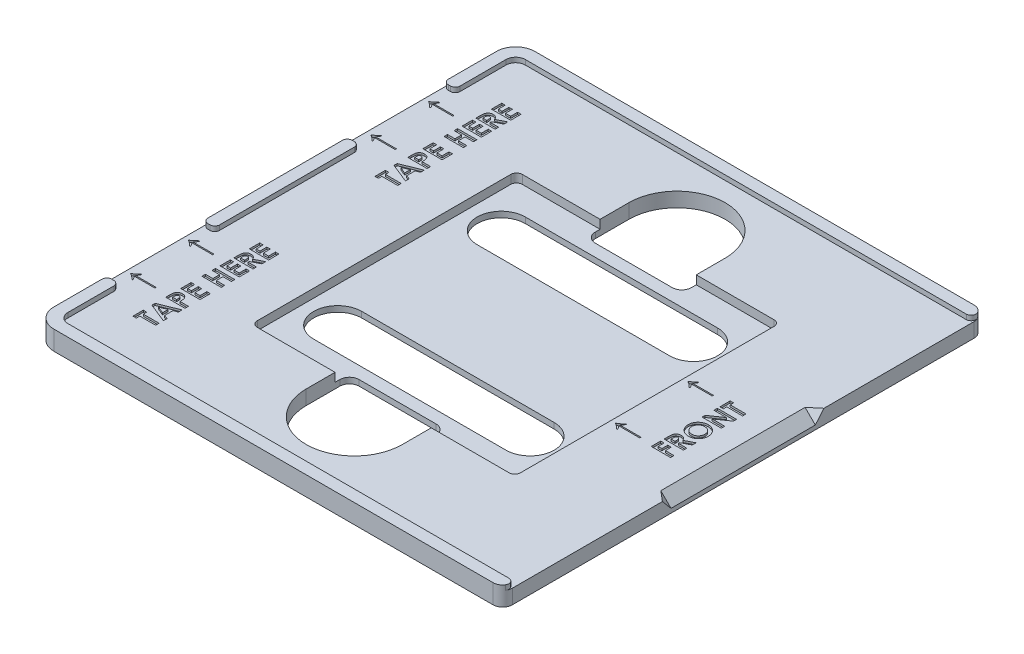
SolidWorks part; units mm, degrees
ref_plane "Front Plane" through (0, 0, 0) normal (0, 0, 1) x (1, 0, 0)
ref_plane "Top Plane" through (0, 0, 0) normal (0, 1, 0) x (1, 0, 0)
ref_plane "Right Plane" through (0, 0, 0) normal (1, 0, 0) x (0, 0, -1)
sketch "Sketch1" plane through (0, 0, 0) normal (0, 1, 0) x (1, 0, 0)
  line L1 (-50, -50) -> (50, -50)
  line L2 (-50, -50) -> (-50, 50)
  line L3 (-50, 50) -> (50, 50)
  line L4 (50, -50) -> (50, 50)
  line L5 (-50, -50) -> (50, 50) construction
  line L6 (-50, 50) -> (50, -50) construction
  point P0 (0, 0)
  dimension "D1" = 100
  dimension "D2" = 100
extrude "Boss-Extrude1" add sketch "Sketch1" along normal blind 3
sketch "Sketch2" plane through (0, 3, 0) normal (0, 1, 0) x (1, 0, 0)
  line L0 (-26.17, 27.35) -> (26.17, 27.35)
  line L1 (-26.17, 27.35) -> (26.17, 27.35) construction
  line L2 (27.17, 26.35) -> (27.17, -26.35)
  line L3 (27.17, 26.35) -> (27.17, -26.35) construction
  line L4 (26.17, -27.35) -> (-26.17, -27.35)
  line L5 (26.17, -27.35) -> (-26.17, -27.35) construction
  line L6 (-27.17, -26.35) -> (-27.17, 26.35)
  line L7 (-27.17, -26.35) -> (-27.17, 26.35) construction
  line L8 (-26.17, 27.55) -> (26.17, 27.55)
  line L9 (27.37, 26.35) -> (27.37, -26.35)
  line L10 (26.17, -27.55) -> (-26.17, -27.55)
  line L11 (-27.37, -26.35) -> (-27.37, 26.35)
  line L12 (-10, -27.55) -> (-10, -33.55)
  line L13 (-10, -33.55) -> (10, -33.55) construction
  line L14 (10, -33.55) -> (10, -27.55)
  line L15 (-27.37, 0) -> (27.37, 0) construction
  line L16 (-10, 33.55) -> (10, 33.55) construction
  line L17 (10, 33.55) -> (10, 27.55)
  line L18 (-10, 27.55) -> (-10, 33.55)
  arc A0 (-26.17, 27.35) -> (-27.17, 26.35) centre (-26.17, 26.35) ccw
  arc A1 (-26.17, 27.35) -> (-27.17, 26.35) centre (-26.17, 26.35) ccw construction
  arc A2 (27.17, 26.35) -> (26.17, 27.35) centre (26.17, 26.35) ccw
  arc A3 (27.17, 26.35) -> (26.17, 27.35) centre (26.17, 26.35) ccw construction
  arc A4 (26.17, -27.35) -> (27.17, -26.35) centre (26.17, -26.35) ccw
  arc A5 (26.17, -27.35) -> (27.17, -26.35) centre (26.17, -26.35) ccw construction
  arc A6 (-27.17, -26.35) -> (-26.17, -27.35) centre (-26.17, -26.35) ccw
  arc A7 (-27.17, -26.35) -> (-26.17, -27.35) centre (-26.17, -26.35) ccw construction
  arc A8 (27.37, 26.35) -> (26.17, 27.55) centre (26.17, 26.35) ccw
  arc A9 (26.17, -27.55) -> (27.37, -26.35) centre (26.17, -26.35) ccw
  arc A10 (-27.37, -26.35) -> (-26.17, -27.55) centre (-26.17, -26.35) ccw
  arc A11 (-26.17, 27.55) -> (-27.37, 26.35) centre (-26.17, 26.35) ccw
  arc A12 (10, -33.55) -> (-10, -33.55) centre (0, -33.55) cw
  arc A13 (10, 33.55) -> (-10, 33.55) centre (0, 33.55) ccw
  point P29 (0, 0)
  point P30 (0, 0)
  point P31 (27.37, 0)
  dimension "D4" = 27.37
  dimension "D2" = 6
  dimension "D3" = 20
  dimension "D1" = 0.2
extrude "Cut-Extrude1" cut sketch "Sketch2" against normal blind 1.8 contours A12 L14 L10 L12 | L17 A13 L18 L8 | L8 A11 L11 A10 L10 A9 L9 A8
sketch "Sketch3" plane through (0, 3, 0) normal (0, 1, 0) x (1, 0, 0)
  line L0 (50, 50) -> (-50, 50) construction
  line L1 (50, -50) -> (47.3, -50)
  line L2 (50, -50) -> (50, 50)
  line L3 (50, 50) -> (47.3, 50)
  line L4 (47.3, -50) -> (47.3, 50)
  line L5 (50, -50) -> (47.3, 50) construction
  line L6 (50, 50) -> (47.3, -50) construction
  point P4 (48.65, 0)
  dimension "D1" = 2.7
extrude "Cut-Extrude3" cut sketch "Sketch3" against normal through all
sketch "Sketch4" plane through (0, 1.2, 0) normal (0, 1, 0) x (1, 0, 0)
  line L0 (-27.17, 0) -> (27.37, 0) construction
  line L3 (0, -27.35) -> (0, 27.35) construction
  line L6 (-27.17, -17) -> (27.37, -17) construction
  line L7 (-27.17, 17) -> (27.37, 17) construction
  line L8 (-20, -17) -> (20, -17) construction
  line L9 (-20, -12) -> (20, -12)
  line L10 (-20, -22) -> (20, -22)
  line L11 (-20, 17) -> (20, 17) construction
  line L12 (-20, 22) -> (20, 22)
  line L13 (-20, 12) -> (20, 12)
  line L14 (26.17, -27.35) -> (-26.17, -27.35) construction
  line L15 (27.37, 26.35) -> (27.37, -26.35) construction
  line L16 (-26.17, 27.35) -> (26.17, 27.35) construction
  line L17 (-27.17, -26.35) -> (-27.17, 26.35) construction
  arc A0 (-20, -12) -> (-20, -22) centre (-20, -17) ccw
  arc A1 (20, -22) -> (20, -12) centre (20, -17) ccw
  arc A2 (-20, 22) -> (-20, 12) centre (-20, 17) ccw
  arc A3 (20, 12) -> (20, 22) centre (20, 17) ccw
  point P2 (0, 0)
  point P3 (-27.17, 17)
  point P4 (0, 0)
  point P5 (27.37, 17)
  point P8 (0, 0)
  point P9 (0, -27.35)
  point P10 (0, 0)
  point P11 (0, 27.4617)
  point P18 (0, -17)
  point P23 (0, 17)
  point P30 (0, 0)
  point P33 (0, 0)
  point P34 (27.37, -17)
  point P37 (0, 0)
  point P38 (0, 0)
  point P39 (0, 0)
  point P40 (27.37, 0)
  point P41 (0, 0)
  point P42 (0, 27.35)
  point P45 (0, 0)
  point P46 (-27.17, -17)
  point P49 (0, 0)
  point P50 (-27.17, 0)
  point P51 (0, 0)
  dimension "D1" = 17
  dimension "D2" = 17
  dimension "D3" = 40
  dimension "D4" = 10
  dimension "D5" = 40
  dimension "D6" = 10
extrude "Cut-Extrude4" cut sketch "Sketch4" against normal through all
sketch "Sketch6" plane through (0, 1.2, 0) normal (0, 1, 0) x (1, 0, 0)
  line L27 (10, -33.55) -> (10, -27.55)
  line L28 (-10, -27.55) -> (-10, -33.55)
  line L29 (10, -33.55) -> (10, -27.55)
  line L30 (-10, -27.55) -> (-10, -33.55)
  line L33 (-10, 27.55) -> (10, 27.55)
  line L34 (10, -27.55) -> (-10, -27.55)
  line L35 (-10, 27.55) -> (-10, 33.55)
  line L36 (10, 33.55) -> (10, 27.55)
  line L37 (-10, 27.55) -> (-10, 33.55)
  line L38 (10, 33.55) -> (10, 27.55)
  arc A13 (-10, -33.55) -> (10, -33.55) centre (0, -33.55) ccw
  arc A14 (-10, -33.55) -> (10, -33.55) centre (0, -33.55) ccw
  arc A17 (10, 33.55) -> (-10, 33.55) centre (0, 33.55) ccw
  arc A18 (10, 33.55) -> (-10, 33.55) centre (0, 33.55) ccw
  point P0 (-9.987, -27.55)
  dimension "D1" = 0
  dimension "D2" = 0
extrude "Cut-Extrude5" cut sketch "Sketch6" against normal through all
sketch "Sketch7" plane through (0, 0, 27.55) normal (0, 0, 1) x (1, 0, 0)
  line L1 (-10, 0) -> (10, 0)
  line L2 (-10, 0) -> (-10, 1.2)
  line L3 (-10, 1.2) -> (10, 1.2)
  line L4 (10, 0) -> (10, 1.2)
  line L5 (-10, 0) -> (10, 1.2) construction
  line L6 (-10, 1.2) -> (10, 0) construction
  point P4 (0, 0.6)
sketch "Sketch8" plane through (0, 0, -27.55) normal (0, 0, -1) x (-1, 0, 0)
  line L1 (-10, 0) -> (10, 0)
  line L2 (-10, 0) -> (-10, 1.2)
  line L3 (-10, 1.2) -> (10, 1.2)
  line L4 (10, 0) -> (10, 1.2)
  line L5 (-10, 0) -> (10, 1.2) construction
  line L6 (-10, 1.2) -> (10, 0) construction
  point P4 (0, 0.6)
extrude "Cut-Extrude6" cut sketch "Sketch8" against normal blind 3
fillet "Fillet1" radius 2 2 edges at (10, 0.6, -24.55) (-10, 0.6, -24.55)
extrude "Cut-Extrude7" cut sketch "Sketch7" against normal blind 3
fillet "Fillet2" radius 2 2 edges at (-10, 0.6, 24.55) (10, 0.6, 24.55)
sketch "Sketch9" plane through (0, 3, 0) normal (0, 1, 0) x (1, 0, 0)
  line L0 (47.3, 47.55) -> (47.3, 50)
  line L1 (47.3, 50) -> (47.3, -50) construction
  line L2 (47.3, 50) -> (-50, 50)
  line L3 (-50, 50) -> (-50, -50)
  line L4 (-50, -50) -> (47.3, -50)
  line L5 (47.3, -50) -> (47.3, -47.55)
  line L6 (47.3, -47.55) -> (-47.55, -47.55)
  line L7 (-47.55, -47.55) -> (-47.55, 47.55)
  line L8 (-47.55, 47.55) -> (47.3, 47.55)
  line L9 (-45.35, 47.35) -> (45.35, 47.35) construction
  line L10 (45.35, -47.35) -> (-45.35, -47.35) construction
  line L11 (-47.35, -45.35) -> (-47.35, 45.35) construction
  point P9 (0, 0)
  point P16 (47.3, 48.7966)
  dimension "D1" = 0.2
  dimension "D2" = 0.2
  dimension "D3" = 0.2
extrude "Boss-Extrude2" add sketch "Sketch9" along normal blind 1
ref_plane "Plane1" through (22.15, -22.15, 0) normal (0.7071, -0.7071, 0) x (0, 0, 1)
sketch "Sketch11" plane through (22.15, -22.15, 0) normal (0.7071, -0.7071, 0) x (0, 0, 1)
  line L0 (0, -35.5675) -> (0, -34.0675) construction
  line L1 (-47.55, -35.5675) -> (47.55, -35.5675) construction
  line L2 (15, -34.0675) -> (-15, -34.0675)
  line L3 (15, -34.0675) -> (16.7876, -35.5675)
  line L4 (16.7876, -35.5675) -> (-16.7876, -35.5675)
  line L5 (-16.7876, -35.5675) -> (-15, -34.0675)
  point P8 (0, -34.0675)
  dimension "D1" = 1.5
  dimension "D2" = 30
  dimension "D3" = 140
  dimension "D4" = 140
extrude "Cut-Extrude8" cut sketch "Sketch11" against normal through all both and the other way through all
sketch "Sketch12" plane through (0, 4, 0) normal (0, 1, 0) x (1, 0, 0)
  line L0 (-47.55, -47.55) -> (-47.55, 47.55) construction
  line L1 (-47.55, -35) -> (-50, -35)
  line L2 (-47.55, -35) -> (-47.55, -15)
  line L3 (-47.55, -15) -> (-50, -15)
  line L4 (-50, -35) -> (-50, -15)
  line L5 (-47.55, -35) -> (-50, -15) construction
  line L6 (-47.55, -15) -> (-50, -35) construction
  line L7 (-50, 50) -> (-50, -50) construction
  line L8 (0, 0) -> (-50, 0) construction
  line L9 (-47.55, 35) -> (-50, 35)
  line L10 (-47.55, 35) -> (-47.55, 15)
  line L11 (-47.55, 15) -> (-50, 15)
  line L12 (-50, 35) -> (-50, 15)
  line L13 (-47.55, 35) -> (-50, 15) construction
  line L14 (-47.55, 15) -> (-50, 35) construction
  point P4 (-48.775, -25)
  point P13 (-48.775, 25)
  dimension "D1" = 20
  dimension "D2" = 20
  dimension "D3" = 15
  dimension "D4" = 15
extrude "Cut-Extrude9" cut sketch "Sketch12" against normal up to surface (1 mm away) up to face at (0, 3, 0)
fillet "Fillet3" radius 2 2 edges at (-47.55, 3.5, 47.55) (-47.55, 3.5, -47.55)
fillet "Fillet4" radius 4 2 edges at (-50, 2, -50) (-50, 2, 50)
fillet "Fillet6" radius 2 2 edges at (47.3, 2, -50) (47.3, 2, 50)
fillet "Fillet5" radius 1 10 edges at (47.3, 3.5, 47.55) (47.3, 3.5, -47.55) (-47.55, 3.5, -15) (-50, 3.5, -15) (-50, 3.5, -35) (-47.55, 3.5, -35) (-50, 3.5, 15) (-47.55, 3.5, 15) (-47.55, 3.5, 35) (-50, 3.5, 35)
sketch "Sketch13" plane through (0, 3, 0) normal (0, 1, 0) x (1, 0, 0)
  line L0 (0, 0) -> (-47.55, 0) construction
  line L1 (-47.55, -14) -> (-47.55, 14) construction
  line L2 (-45.05, -38.5) -> (-45.05, 38.5) construction
  line L5 (0, 0) -> (32.3, 0) construction
  line L6 (47.3, -16.7876) -> (47.3, -48) construction
  line L7 (32.3, -38.5) -> (32.3, 38.5) construction
  text T0 "<b>    ↑      ↑</b>\r\n<b>TAPE HERE</b>" font "Century Gothic" height 4
  text T1 "<b>    ↑      ↑    </b>\r\n<b>TAPE HERE</b>" font "Century Gothic" height 4
  text T2 "<b>↑        ↑</b>\r\n<b>FRONT</b>\r\n" font "Century Gothic" height 4
  point P8 (-45.05, 0)
  point P15 (32.3, 0)
  dimension "D1" = 2.5
  dimension "D2" = 77
  dimension "D3" = 15
  dimension "D4" = 77
extrude "Cut-Extrude10" cut sketch "Sketch13" along direction (0, -1, 0) on the side against the normal blind 0.4
sketch "Sketch14" plane through (0, 0, 0) normal (0, -1, 0) x (1, 0, 0)
  line L0 (-50, -2.5) -> (47.3, -2.5) construction
  line L1 (-50, -46) -> (-50, 46) construction
  line L2 (47.3, -48) -> (47.3, 48) construction
  line L3 (-46, 50) -> (45.3, 50) construction
  line L4 (10, 33.55) -> (10, 26.55) construction
  line L5 (-20, 22) -> (20, 22) construction
  text T0 "Stencil tool FRDM MCXn hat" font "Century Gothic" height 4
  dimension "D1" = 52.5
  dimension "D2" = 10
  dimension "D3" = 22
extrude "Cut-Extrude11" cut sketch "Sketch14" against normal blind 0.4
